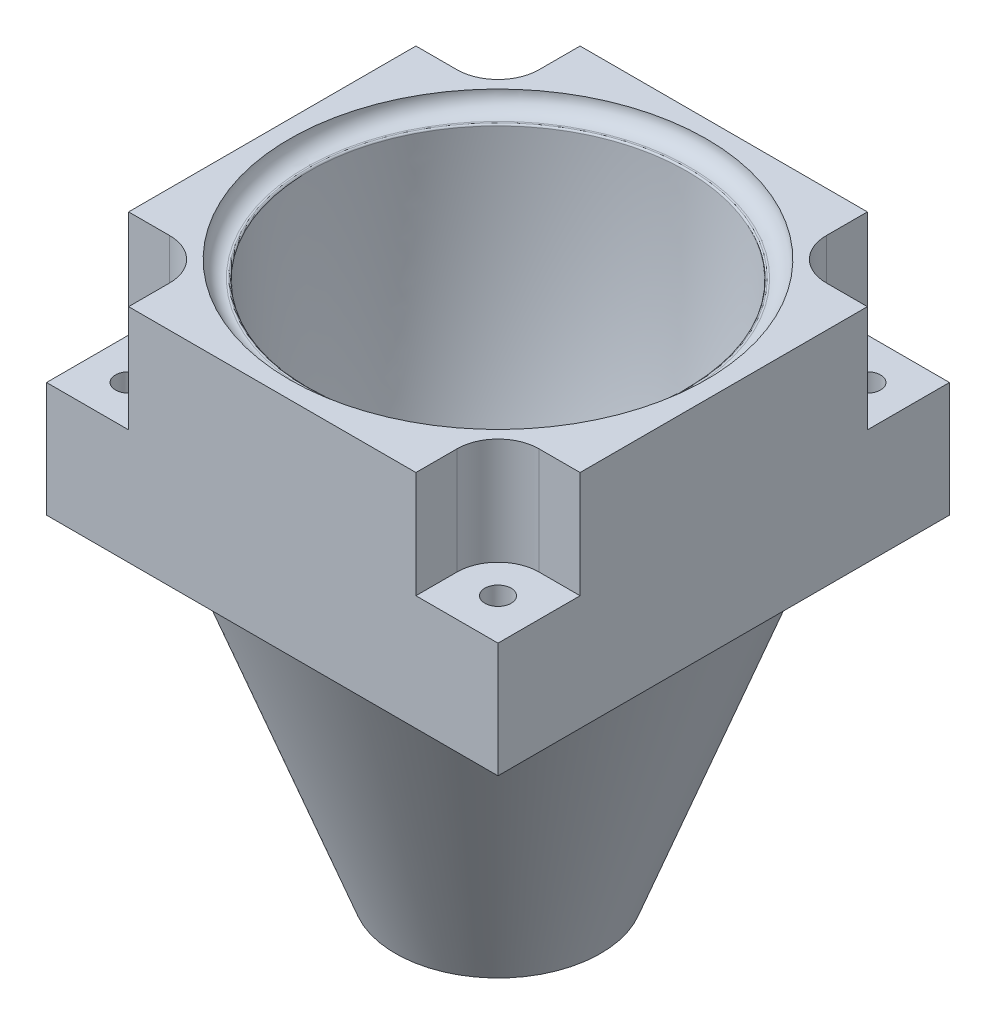
SolidWorks part; units mm, degrees
ref_plane "Front Plane" through (0, 0, 0) normal (0, 0, 1) x (1, 0, 0)
ref_plane "Top Plane" through (0, 0, 0) normal (0, 1, 0) x (1, 0, 0)
ref_plane "Right Plane" through (0, 0, 0) normal (1, 0, 0) x (0, 0, -1)
sketch "Sketch5" plane through (0, 0, 0) normal (0, 0, 1) x (1, 0, 0)
  line L0 (0, -10) -> (0, 0) construction
  line L2 (27.5, -10) -> (-27.5, -10)
  line L3 (27.5, -10) -> (27.5, 65)
  line L4 (27.5, 65) -> (-27.5, 65)
  line L5 (-27.5, -10) -> (-27.5, 65)
  line L6 (27.5, -10) -> (-27.5, 65) construction
  line L7 (27.5, 65) -> (-27.5, -10) construction
  dimension "D1" = 55
  dimension "D2" = 75
  dimension "D3" = 10
extrude "Boss-Extrude8" add sketch "Sketch5" along normal mid plane 55
sketch "Sketch1" plane through (0, 0, 0) normal (1, 0, 0) x (0, 0, -1)
  line L0 (2.2, 0) -> (3.0834, 0)
  line L1 (23, 55) -> (20, 55) construction
  line L2 (0, -7) -> (0, 3)
  line L3 (0, 0) -> (0, 78.0585) construction
  line L4 (23.4, 55) -> (23.1926, 55)
  line L5 (0, 3) -> (-8.2525, 3) construction
  line L6 (25.4, 57) -> (86.3489, 57)
  line L7 (86.3489, 57) -> (86.3489, 102.8514)
  line L8 (86.1489, 103.0514) -> (0, 103.0514)
  line L9 (0, 103.0514) -> (0, -7)
  line L10 (2.2, 0) -> (2.2, -7)
  line L14 (20, 55) -> (20, 57) construction
  line L17 (22, 59) -> (23.4, 59) construction
  line L19 (2.2, -7) -> (0, -7)
  arc A0 (20, 57) -> (22, 59) centre (22, 57) cw construction
  arc A1 (25.4, 57) -> (23.4, 55) centre (23.4, 57) cw
  arc A2 (25.4, 57) -> (23.4, 59) centre (23.4, 57) ccw construction
  arc A3 (22.9927, 54.8077) -> (23.1926, 55) centre (23.1926, 54.8) cw
  arc A4 (86.3489, 102.8514) -> (86.1489, 103.0514) centre (86.1489, 102.8514) ccw
  arc A5 (6.5466, 1.3936) -> (3.0834, 0) centre (3.0834, 5) cw
  spline S0 degree 3 poles (22.9927, 54.8077) (22.4677, 41.1265) (19.1132, 19.4129) (11.2761, 5.9352) (6.5466, 1.3936) knots 0.002336 0.002336 0.002336 0.002336 0.501168 0.951802 0.951802 0.951802 0.951802
  spline S1 degree 3 poles (20, 55) (20, 43.9577) (18.5158, 25.9427) (6.738, 3) (0, 3) knots 0 0 0 0 0.518417 1 1 1 1 construction
  dimension "D4" = 2.2
  dimension "D5" = 7
  dimension "D1" = 2
  dimension "D7" = 0.2
  dimension "D8" = 5
  dimension "D3" = 7
  dimension "D6" = 66
  dimension "D2" = 22
  dimension "D10" = 3
revolve "Cut-Revolve1" cut sketch "Sketch1" angle 360 about L9
sketch "Sketch6" plane through (0, 57, 0) normal (0, 1, 0) x (1, 0, 0)
  line L1 (-27.5, 27.5) -> (-17.5, 27.5)
  line L2 (-27.5, 27.5) -> (-27.5, 17.5)
  line L3 (-27.5, 17.5) -> (-17.5, 17.5)
  line L4 (-17.5, 27.5) -> (-17.5, 17.5)
  dimension "D1" = 10
  dimension "D2" = 10
extrude "Cut-Extrude2" cut sketch "Sketch6" against normal blind 13
sketch "Sketch7" plane through (0, -10, 0) normal (0, -1, 0) x (1, 0, 0)
  circle A0 centre (0, 0) radius 2.2
  circle A1 centre (0, 0) radius 2.2 construction
extrude "Cut-Extrude1" cut sketch "Sketch7" against normal blind 90
fillet "Fillet1" radius 5 1 edges at (-17.5, 49.7616, -17.5)
ref_axis "Axis1" through (0, 0, 0) along (0, 1, 0)
sketch "Sketch8" plane through (0, 44, 0) normal (0, 1, 0) x (1, 0, 0)
  line L0 (-22.5, 27.5) -> (-22.5, 22.5) construction
  line L1 (-17.5, 27.5) -> (-27.5, 27.5) construction
  line L2 (-22.5, 22.5) -> (-27.5, 22.5) construction
  line L3 (-27.5, 27.5) -> (-27.5, 17.5) construction
  circle A0 centre (-22.5, 22.5) radius 1.6
  dimension "D1" = 3.2
extrude "Cut-Extrude3" cut sketch "Sketch8" against normal through all
sketch "Sketch10" plane through (0, -10, 0) normal (0, -1, 0) x (-1, 0, 0)
  line L1 (17.5, 27.5) -> (27.5, 27.5)
  line L2 (17.5, 27.5) -> (17.5, 17.5)
  line L3 (17.5, 17.5) -> (27.5, 17.5)
  line L4 (27.5, 27.5) -> (27.5, 17.5)
  dimension "D1" = 10
  dimension "D2" = 10
extrude "Cut-Extrude4" cut sketch "Sketch10" against normal blind 40
pattern_circular "CirPattern1" count 4 over 360 about axis through (0, 0, 0) along (0, 1, 0) of "Cut-Extrude2", "Cut-Extrude4", "Cut-Extrude3", "Fillet1"
sketch "Sketch11" plane through (0, 0, 0) normal (0, 0, 1) x (1, 0, 0)
  line L0 (27.5, 30) -> (12.5, -10)
  line L1 (27.5, 30) -> (27.5, -10) construction
  line L2 (-17.5, -10) -> (17.5, -10) construction
  line L3 (12.5, -10) -> (27.5, -10) construction
  line L4 (27.5, -10) -> (27.5, 30) construction
  line L5 (12.5, -10) -> (12.5, -34.55)
  line L6 (12.5, -34.55) -> (75.7645, -34.55)
  line L7 (75.7645, -34.55) -> (75.7645, 30)
  line L8 (75.7645, 30) -> (27.5, 30)
  dimension "D1" = 40
  dimension "D2" = 15
revolve "Cut-Revolve20" cut sketch "Sketch11" angle 360 about axis through (0, 0, 0) along (0, 1, 0)
